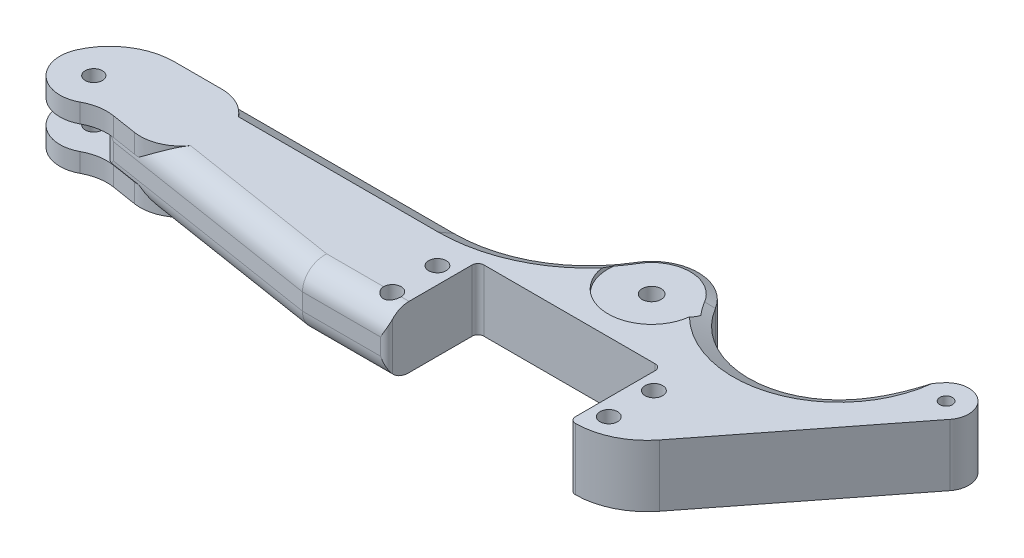
SolidWorks part; units mm, degrees
ref_plane "Front Plane" through (0, 0, 0) normal (0, 0, 1) x (1, 0, 0)
ref_plane "Top Plane" through (0, 0, 0) normal (0, 1, 0) x (1, 0, 0)
ref_plane "Right Plane" through (0, 0, 0) normal (1, 0, 0) x (0, 0, -1)
sketch "Sketch1" plane through (0, 0, 0) normal (0, 1, 0) x (1, 0, 0)
  line L0 (-20.3, 0) -> (-20.3, 20.3)
  line L1 (-20.3, 20.3) -> (20.3, 20.3)
  line L2 (20.3, 20.3) -> (20.3, 0)
  line L3 (34.0792, 6.1494) -> (62.3401, 42.3217)
  line L4 (45.9237, 37.5524) -> (54.4599, 48.4783)
  line L5 (-20.3, 0) -> (20.3, 0) construction
  line L6 (-30.3774, 25) -> (-92.3181, 25)
  line L7 (-20.3, 0) -> (-38.9332, 0)
  line L8 (-38.9332, 0) -> (-88.7291, 7.8869)
  line L9 (20.3, 0) -> (21.471, 0)
  line L10 (0, 0) -> (0, 20.3) construction
  line L11 (-92.3181, 22) -> (-84.3107, 0) construction
  arc A1 (54.4599, 48.4783) -> (62.3401, 42.3217) centre (58.4, 45.4) cw
  arc A2 (13.0374, 39.5906) -> (45.9237, 37.5524) centre (30.1797, 49.8529) ccw
  arc A3 (13.0374, 39.5906) -> (-4.6374, 39.5906) centre (4.2, 34.3) ccw
  arc A4 (-4.6374, 39.5906) -> (-30.3774, 25) centre (-30.3774, 55) cw
  arc A5 (-92.3181, 25) -> (-94.0876, 19.5775) centre (-92.3181, 22) ccw
  arc A6 (-94.0876, 19.5775) -> (-91.1725, 11.5683) centre (-98.6, 13.4) cw
  arc A7 (-91.1725, 11.5683) -> (-88.7291, 7.8869) centre (-88.2598, 10.85) ccw
  arc A8 (21.471, 0) -> (34.0792, 6.1494) centre (21.471, 16) ccw
  circle A9 centre (-24, 15) radius 1.95
  circle A10 centre (-24, 5) radius 1.95
  circle A11 centre (58.4, 45.4) radius 1.4
  circle A12 centre (4.2, 34.3) radius 2.1
  circle A13 centre (24, 15) radius 1.95
  circle A14 centre (24, 5) radius 1.95
  circle A15 centre (-98.6, 13.4) radius 1.9 construction
  circle A16 centre (-98.6, 13.4) radius 7.5 construction
  point P34 (0, 0)
  dimension "D8" = 10.3
  dimension "D12" = 3.9
  dimension "D13" = 2.8
  dimension "D14" = 4.2
  dimension "D15" = 16
  dimension "D21" = 30
  dimension "D22" = 3
  dimension "D23" = 15
  dimension "D24" = 7.65
  dimension "D26" = 3.8
  dimension "D1" = 40.6
  dimension "D2" = 58.4
  dimension "D3" = 45.4
  dimension "D4" = 10
  dimension "D5" = 24
  dimension "D6" = 10
  dimension "D7" = 5
  dimension "D9" = 34.3
  dimension "D10" = 4.2
  dimension "D11" = 128
  dimension "D16" = 20.3
  dimension "D17" = 25
  dimension "D18" = 98.6
  dimension "D19" = 9
  dimension "D20" = 13.4
  dimension "D25" = 110
extrude "Boss-Extrude1" add sketch "Sketch1" along normal mid plane 13.7
chamfer "Chamfer1" distance 2 angle 60 8 edges at (28.9439, -6.85, -29.9118) (4.2, -6.85, -44.6) (-15.5836, -6.85, -28.9013) (-61.3478, -6.85, -25) (28.9439, 6.85, -29.9118) (4.2, 6.85, -44.6) (-15.5836, 6.85, -28.9013) (-61.3478, 6.85, -25)
fillet "Fillet1" radius 1.3 4 edges at (20.3, 0, -20.3) (20.3, 0, 0) (-20.3, 0, 0) (-20.3, 0, -20.3)
fillet "Fillet2" radius 5 4 edges at (-30.2666, -6.85, 0) (-63.8312, -6.85, -3.9434) (-63.8312, 6.85, -3.9434) (-30.2666, 6.85, 0)
sketch "Sketch2" plane through (0, 6.85, 0) normal (0, 1, 0) x (1, 0, 0)
  circle A0 centre (4.2, 34.3) radius 9.65
  dimension "D1" = 19.3
extrude "Cut-Extrude1" cut sketch "Sketch2" against normal blind 1
mirror "Mirror1" about plane through (0, 0, 0) normal (0, 1, 0) of "Cut-Extrude1"
sketch "Sketch3" plane through (0, 6.85, 0) normal (0, 1, 0) x (1, 0, 0)
  line L0 (-92.3181, 25) -> (-30.3774, 25) construction
  line L1 (-38.9332, 0) -> (-88.7291, 7.8869) construction
  line L2 (-38.9332, 0) -> (-88.7291, 7.8869) construction
  line L3 (-30.3774, 25) -> (-92.3181, 25) construction
  line L4 (-92.3181, 25) -> (-81.7924, 25)
  line L5 (-88.7291, 7.8869) -> (-83.2081, 7.0124)
  circle A0 centre (-98.6, 13.4) radius 1.9 construction
  circle A1 centre (-98.6, 13.4) radius 1.9
  circle A2 centre (-98.6, 13.4) radius 7.5 construction
  circle A3 centre (-98.6, 13.4) radius 7.5 construction
  arc A4 (-92.3181, 25) -> (-105.4655, 16.4191) centre (-92.3181, 10.6375) ccw
  arc A5 (-95.025, 6.8069) -> (-88.7291, 7.8869) centre (-90.2848, -1.9352) cw
  circle A6 centre (-81.7924, 15.9505) radius 9.0495 construction
  arc A7 (-105.4655, 16.4191) -> (-95.025, 6.8069) centre (-98.6, 13.4) ccw
  arc A8 (-81.7924, 25) -> (-83.2081, 7.0124) centre (-81.7924, 15.9505) cw
  dimension "D1" = 17
extrude "Boss-Extrude2" add sketch "Sketch3" against normal blind 4.2
mirror "Mirror2" about plane through (0, 0, 0) normal (0, 1, 0) of "Boss-Extrude2"
